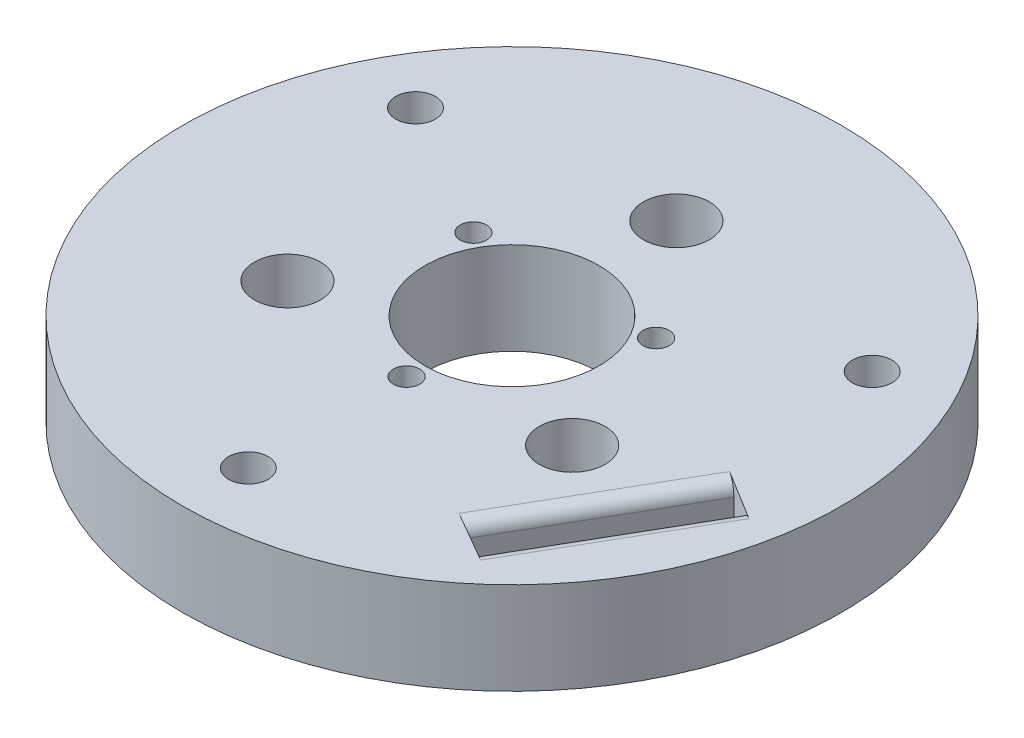
SolidWorks part; units mm, degrees
ref_plane "前视基准面" through (0, 0, 0) normal (0, 0, 1) x (1, 0, 0)
ref_plane "上视基准面" through (0, 0, 0) normal (0, 1, 0) x (1, 0, 0)
ref_plane "右视基准面" through (0, 0, 0) normal (1, 0, 0) x (0, 0, -1)
sketch "草图1" plane through (0, 0, 0) normal (0, 1, 0) x (1, 0, 0)
  line L0 (0, 0) -> (-10.8, -18.7061) construction
  line L1 (-10.8, -18.7061) -> (10.8, -18.7061) construction
  line L2 (10.8, -18.7061) -> (0, 0) construction
  line L3 (-10.8, -18.7061) -> (5.4, -9.3531) construction
  line L4 (10.8, -18.7061) -> (-5.4, -9.3531) construction
  circle A0 centre (0, -12.4708) radius 25
  circle A1 centre (0, -12.4708) radius 6.6
  circle A2 centre (-10.8, -18.7061) radius 1.3
  circle A3 centre (10.8, -18.7061) radius 1.3
  circle A4 centre (0, 0) radius 1.3
  dimension "D4" = 50
  dimension "D5" = 13.2
  dimension "D6" = 2.6
  dimension "D7" = 2.6
  dimension "D8" = 2.6
  dimension "D1" = 21.6
  dimension "D2" = 21.6
  dimension "D3" = 21.6
extrude "凸台-拉伸1" add sketch "草图1" along normal blind 7
sketch "草图2" plane through (0, 7, 0) normal (0, 1, 0) x (1, 0, 0)
  circle A0 centre (-10.8, -18.7061) radius 2.5
  circle A1 centre (10.8, -18.7061) radius 2.5
  circle A2 centre (0, 0) radius 2.5
  dimension "D1" = 5
  dimension "D2" = 5
  dimension "D3" = 5
extrude "切除-拉伸2" cut sketch "草图2" against normal blind 5
sketch "草图4" plane through (0, 7, 0) normal (0, 1, 0) x (1, 0, 0)
  line L0 (0, 0) -> (-10.8, -18.7061) construction
  line L1 (0, -12.4708) -> (-21.6506, 0.0292) construction
  line L2 (0, -2.4708) -> (0, -22.4708) construction
  circle A1 centre (0, -12.4708) radius 25 construction
  circle A2 centre (-6.9282, -8.4708) radius 1
  circle A3 centre (6.9282, -8.4708) radius 1
  circle A4 centre (0, -20.4708) radius 1
  dimension "D3" = 2
  dimension "D5" = 2
  dimension "D2" = 8
  dimension "D4" = 8
extrude "切除-拉伸3" cut sketch "草图4" against normal blind 6
sketch "草图5" plane through (0, 7, 0) normal (0, 1, 0) x (1, 0, 0)
  line L0 (0, -12.4708) -> (-6.9282, -8.4708) construction
  line L1 (-6.9282, -8.4708) -> (-21.6506, 0.0292) construction
  line L4 (0, -12.4708) -> (0, -20.4708) construction
  line L5 (0, -20.4708) -> (0, -37.4708) construction
  line L6 (0, -12.4708) -> (-17.3205, -2.4708) construction
  line L7 (0, -12.4708) -> (17.3205, -2.4708) construction
  circle A0 centre (0, -12.4708) radius 25 construction
  circle A5 centre (0, -12.4708) radius 20 construction
  circle A6 centre (-17.3205, -2.4708) radius 1.5
  circle A7 centre (0, -32.4708) radius 1.5
  circle A8 centre (17.3205, -2.4708) radius 1.5
  dimension "D1" = 3
  dimension "D2" = 3
  dimension "D4" = 40
  dimension "D5" = 3
extrude "切除-拉伸4" cut sketch "草图5" against normal through all
sketch "草图6" plane through (0, 0, 0) normal (0, -1, 0) x (1, 0, 0)
  line L1 (3.2909, 32.4708) -> (1.6454, 35.3208)
  line L2 (1.6454, 35.3208) -> (-1.6454, 35.3208)
  line L3 (-1.6454, 35.3208) -> (-3.2909, 32.4708)
  line L4 (-3.2909, 32.4708) -> (-1.6454, 29.6208)
  line L5 (-1.6454, 29.6208) -> (1.6454, 29.6208)
  line L6 (1.6454, 29.6208) -> (3.2909, 32.4708)
  line L7 (20.6114, 2.4708) -> (18.966, 5.3208)
  line L8 (18.966, 5.3208) -> (15.6751, 5.3208)
  line L9 (15.6751, 5.3208) -> (14.0296, 2.4708)
  line L10 (14.0296, 2.4708) -> (15.6751, -0.3792)
  line L11 (15.6751, -0.3792) -> (18.966, -0.3792)
  line L12 (18.966, -0.3792) -> (20.6114, 2.4708)
  line L13 (-14.0296, 2.4708) -> (-15.6751, 5.3208)
  line L14 (-15.6751, 5.3208) -> (-18.966, 5.3208)
  line L15 (-18.966, 5.3208) -> (-20.6114, 2.4708)
  line L16 (-20.6114, 2.4708) -> (-18.966, -0.3792)
  line L17 (-18.966, -0.3792) -> (-15.6751, -0.3792)
  line L18 (-15.6751, -0.3792) -> (-14.0296, 2.4708)
  circle A3 centre (0, 32.4708) radius 2.85 construction
  circle A4 centre (17.3205, 2.4708) radius 2.85 construction
  circle A5 centre (-17.3205, 2.4708) radius 2.85 construction
  dimension "D1" = 5.7
  dimension "D2" = 5.7
  dimension "D3" = 5.7
extrude "切除-拉伸5" cut sketch "草图6" against normal blind 2.7
sketch "草图7" plane through (0, 7, 0) normal (0, 1, 0) x (1, 0, 0)
  line L0 (0, -12.4708) -> (15.5885, -21.4708) construction
  line L1 (19.3385, -14.9756) -> (11.8385, -27.966)
  line L2 (11.8385, -27.966) -> (14.0035, -29.216)
  line L3 (14.0035, -29.216) -> (21.4688, -16.2858)
  line L4 (21.4688, -16.2858) -> (19.3385, -14.9756)
  dimension "D1" = 18
  dimension "D2" = 7.5
  dimension "D3" = 2.5
extrude "切除-拉伸6" cut sketch "草图7" against normal blind 10
fillet "圆角1" radius 1 4 edges at (17.7361, 7, 22.7509) (15.5885, 7, 21.4708) (17.7361, 0, 22.7509) (15.5885, 0, 21.4708)
